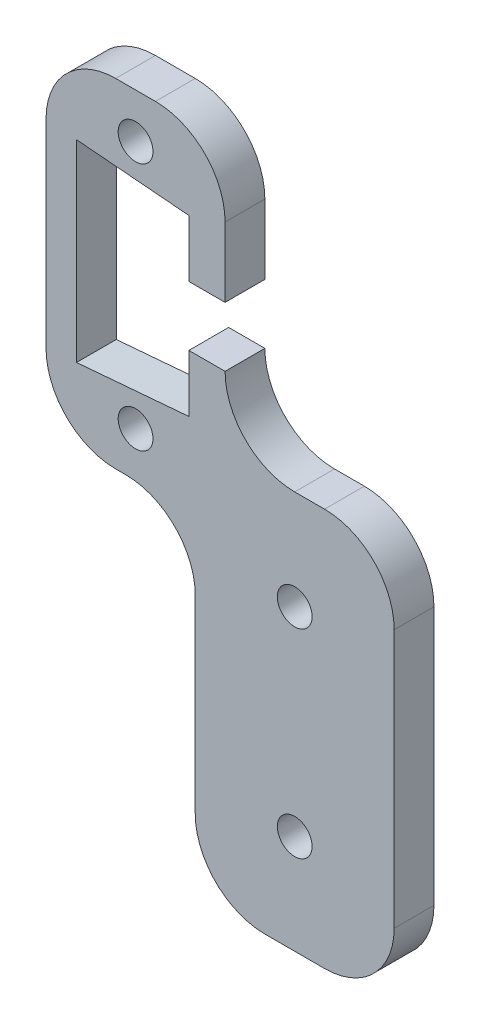
SolidWorks part; units mm, degrees
ref_plane "Plano frontal" through (0, 0, 0) normal (0, 0, 1) x (1, 0, 0)
ref_plane "Plano superior" through (0, 0, 0) normal (0, 1, 0) x (1, 0, 0)
ref_plane "Plano direito" through (0, 0, 0) normal (1, 0, 0) x (0, 0, -1)
sketch "Esboço1" plane through (0, 0, 0) normal (0, 0, 1) x (1, 0, 0)
  line L0 (-9, -17) -> (6, -17)
  line L1 (6, -17) -> (6, -50)
  line L2 (26, -50) -> (26, -10)
  line L3 (9, -10) -> (9, -3)
  line L4 (26, -10) -> (9, -10)
  line L5 (6, -50) -> (26, -50)
  line L6 (5.3591, 0) -> (9, 0) construction
  line L7 (5.3591, -3) -> (9, -3)
  line L8 (5.3591, 3) -> (9, 3)
  line L9 (5.3591, -3) -> (5.3591, -8.75)
  line L10 (9, 3) -> (9, 17)
  line L13 (0, -12.5) -> (0, 12.5) construction
  line L14 (-5.9409, 9.7) -> (5.3591, 8.75)
  line L15 (-5.9409, 9.7) -> (-5.9409, -9.7)
  line L16 (-5.9409, -9.7) -> (5.3591, -8.75)
  line L17 (5.3591, 8.75) -> (5.3591, 3)
  line L18 (-5.9409, 9.7) -> (5.3591, -8.75) construction
  line L19 (-5.9409, -9.7) -> (5.3591, 8.75) construction
  line L21 (-9, 17) -> (9, 17)
  line L22 (-9, 17) -> (-9, -17)
  circle A0 centre (16, -40) radius 10 construction
  circle A1 centre (16, -40) radius 1.75
  circle A6 centre (16, -20) radius 1.75
  circle A12 centre (0, -12.5) radius 1.75
  circle A13 centre (0, 12.5) radius 1.75
  point P10 (0, 17)
  point P16 (-9, 0)
  point P43 (0, 0)
  point P53 (0, 0)
  point P55 (-5.9409, 0)
  dimension "D2" = 3.5
  dimension "D14" = 3.5
  dimension "D15" = 17
  dimension "D4" = 30
  dimension "D6" = 20
  dimension "D3" = 20
  dimension "D5" = 7
  dimension "D7" = 25
  dimension "D8" = 19.4
  dimension "D9" = 17.5
  dimension "D10" = 11.3
  dimension "D11" = 18
  dimension "D12" = 3
  dimension "D13" = 3
  dimension "D16" = 3
extrude "Ressalto-extrusão1" add sketch "Esboço1" along normal blind 4
fillet "Filete2" radius 7 8 edges at (9, -10, 2) (-9, 17, 2) (6, -50, 2) (26, -50, 2) (26, -10, 2) (-9, -17, 2) (6, -17, 2) (9, 17, 2)
